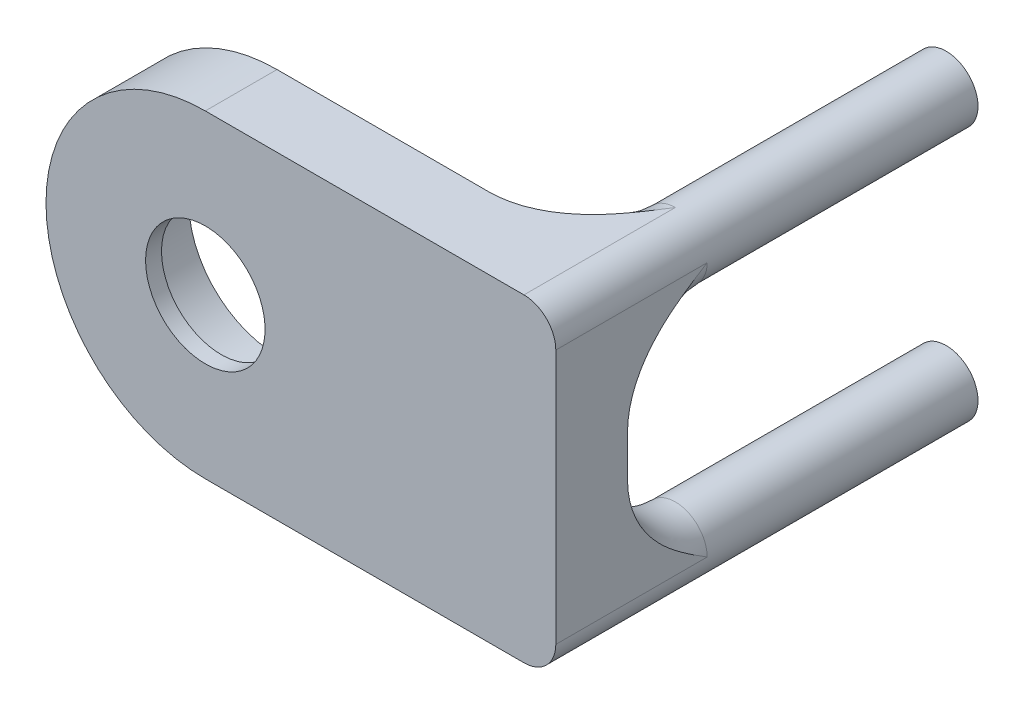
SolidWorks part; units mm, degrees
ref_plane "Ebene vorne" through (0, 0, 0) normal (0, 0, 1) x (1, 0, 0)
ref_plane "Ebene oben" through (0, 0, 0) normal (0, 1, 0) x (1, 0, 0)
ref_plane "Ebene rechts" through (0, 0, 0) normal (1, 0, 0) x (0, 0, -1)
sketch "Skizze1" plane through (0, 0, 0) normal (0, 0, 1) x (1, 0, 0)
  line L0 (0, 20) -> (44, 20)
  line L1 (44, 20) -> (44, -20)
  line L2 (44, -20) -> (0, -20)
  line L3 (0, 0) -> (44, 0) construction
  arc A0 (0, 20) -> (0, -20) centre (0, 0) ccw
  circle A1 centre (40, 16) radius 4
  circle A2 centre (40, 16) radius 1.45
  circle A3 centre (40, -16) radius 1.45
  circle A4 centre (40, -16) radius 4
  dimension "D1" = 40
  dimension "D2" = 8
  dimension "D3" = 2.9
  dimension "D4" = 40
extrude "Aufsatz-Linear austragen1" add sketch "Skizze1" along normal blind 9 contours A2 | A1 A2 | L2 A4 L1 A1 L0 A0 | A4 A3 | A3 region at (12.7446, 0, 0) region at (42.7484, 18.7484, 0) region at (37.2516, -13.2516, 0) region at (40, 16, 0) region at (40, -16, 0)
extrude "Aufsatz-Linear austragen2" add sketch "Skizze1<4>" against normal blind 44 contours A1 A2 | A4 A3 region at (42.7484, 18.7484, 0) region at (37.2516, -13.2516, 0)
sketch "Skizze1<4>" plane through (0, 0, 0) normal (0, 0, 1) x (1, 0, 0) same geometry as "Skizze1"
fillet "Verrundung1" radius 10 2 edges at (37.1716, -13.1716, 0) (37.1716, 13.1716, 0)
sketch "Skizze2" plane through (0, 0, 0) normal (0, 0, -1) x (-1, 0, 0)
  circle A0 centre (0, 0) radius 11.075
  dimension "D1" = 22.15
extrude "Schnitt-Linear austragen1" cut sketch "Skizze2" against normal blind 7
sketch "Skizze3" plane through (0, 0, 7) normal (0, 0, -1) x (-1, 0, 0)
  circle A0 centre (0, 0) radius 7.5
  dimension "D1" = 15
extrude "Schnitt-Linear austragen2" cut sketch "Skizze3" against normal through all
